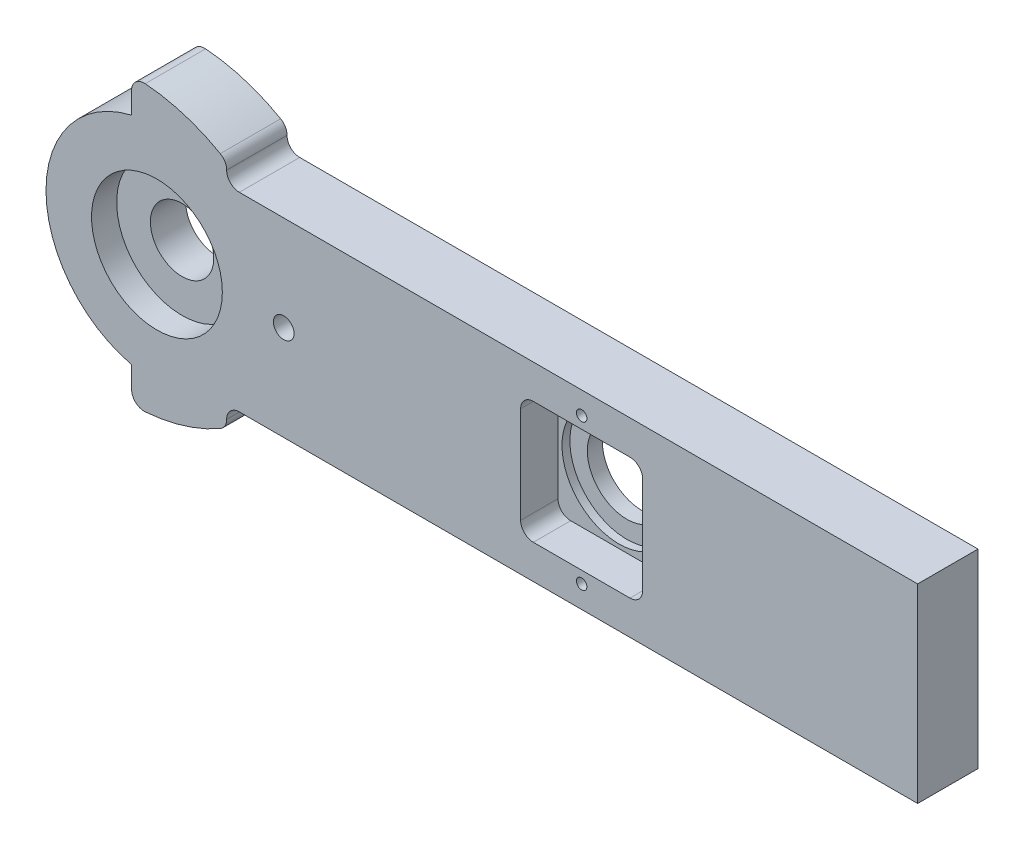
SolidWorks part; units mm, degrees
material "PE High Density"
ref_plane "Front Plane" through (0, 0, 0) normal (0, 0, 1) x (1, 0, 0)
ref_plane "Top Plane" through (0, 0, 0) normal (0, 1, 0) x (1, 0, 0)
ref_plane "Right Plane" through (0, 0, 0) normal (1, 0, 0) x (0, 0, -1)
sketch "Sketch1" plane through (0, 0, 0) normal (0, 0, 1) x (1, 0, 0)
  line L0 (30, 0) -> (30, 30) construction
  line L3 (0, 30) -> (18.0278, 30) construction
  line L6 (0, 0) -> (30, 0) construction
  line L8 (18.0278, 30) -> (240, 30)
  line L9 (240, 30) -> (240, -30)
  line L11 (18.0278, -30) -> (240, -30)
  circle A0 centre (0, 0) radius 30 construction
  arc A2 (18.0278, 30) -> (18.0278, -30) centre (0, 0) ccw
  circle A5 centre (0, 0) radius 10
  dimension "D1" = 60
  dimension "D4" = 70
  dimension "D8" = 20
  dimension "D2" = 240
extrude "Boss-Extrude1" add sketch "Sketch1" along normal mid plane 19.05
sketch "Sketch2" plane through (0, 0, -9.525) normal (0, 0, 1) x (1, 0, 0)
  line L0 (240, -30) -> (240, 30) construction
  circle A0 centre (134, 0) radius 12.5
  dimension "D2" = 25
  dimension "D1" = 106
extrude "Cut-Extrude1" cut sketch "Sketch2" along normal through all
sketch "Sketch3" plane through (0, 0, 9.525) normal (0, 0, 1) x (1, 0, 0)
  line L1 (114.5, -19.5) -> (153.5, -19.5) construction
  line L2 (114.5, -19.5) -> (114.5, 19.5) construction
  line L3 (114.5, 19.5) -> (153.5, 19.5) construction
  line L4 (153.5, -19.5) -> (153.5, 19.5) construction
  line L5 (114.5, -19.5) -> (153.5, 19.5) construction
  line L6 (114.5, 19.5) -> (153.5, -19.5) construction
  circle A0 centre (134, 0) radius 12.5 construction
  circle A3 centre (134, 0) radius 18
  dimension "D1" = 36
  dimension "D2" = 39
  dimension "D3" = 39
extrude "Cut-Extrude2" cut sketch "Sketch3" against normal blind 14.2875
sketch "Sketch4" plane through (0, 0, 9.525) normal (0, 0, 1) x (1, 0, 0)
  circle A0 centre (0, 0) radius 20.6375
  dimension "D1" = 41.275
extrude "Cut-Extrude3" cut sketch "Sketch4" against normal blind 7.9375
sketch "Sketch5" plane through (0, 0, 9.525) normal (0, 0, 1) x (1, 0, 0)
  line L1 (114.75, -19.25) -> (153.25, -19.25)
  line L2 (114.75, -19.25) -> (114.75, 19.25)
  line L3 (114.75, 19.25) -> (153.25, 19.25)
  line L4 (153.25, -19.25) -> (153.25, 19.25)
  line L5 (114.75, -19.25) -> (153.25, 19.25) construction
  line L6 (114.75, 19.25) -> (153.25, -19.25) construction
  point P0 (134, 0)
  dimension "D1" = 38.5
  dimension "D2" = 38.5
extrude "Cut-Extrude4" cut sketch "Sketch5" against normal offset from surface (11.7875 mm away) 2.5 up to face at (146.5, 0, -4.7625)
fillet "Fillet3" radius 4 4 edges at (153.25, -19.25, 3.6313) (114.75, -19.25, 3.6313) (153.25, 19.25, 3.6313) (114.75, 19.25, 3.6313)
sketch "Sketch12" plane through (0, 0, 9.525) normal (0, 0, 1) x (1, 0, 0)
  line L1 (240, 30) -> (18.0278, 30) construction
  line L3 (22, 30) -> (22, 36.35)
  line L4 (-8, 45) -> (22, 45) construction
  line L5 (-8, 45) -> (-8, 34.0735)
  line L6 (240, 30) -> (18.0278, 30) construction
  line L7 (22, 30) -> (18.0278, 30)
  arc A0 (-8, 45) -> (22, 36.35) centre (-8, -11.3481) cw
  arc A1 (18.0278, 30) -> (18.0278, -30) centre (0, 0) ccw construction
  arc A2 (18.0278, 30) -> (-8, 34.0735) centre (0, 0) ccw
  dimension "D2" = 6.35
  dimension "D3" = 30
  dimension "D1" = 45
  dimension "D4" = 8
extrude "Boss-Extrude2" add sketch "Sketch12" against normal through all
mirror "Mirror4" about plane through (0, 0, 0) normal (0, 1, 0) of "Boss-Extrude2"
fillet "Fillet4" radius 4 4 edges at (22, 36.35, 0) (22, -36.35, 0) (-8, -45, 0) (-8, 45, 0)
fillet "Fillet6" radius 4 2 edges at (22, 30, 0) (22, -30, 0)
sketch "Sketch14" plane through (0, 0, 9.525) normal (0, 0, 1) x (1, 0, 0)
  line L0 (0, 0) -> (40, 0) construction
  line L1 (0, 0) -> (40, 0) construction
  circle A0 centre (0, 0) radius 40 construction
  circle A1 centre (40, 0) radius 3.2639
  dimension "D1" = 80
  dimension "D2" = 6.5278
  dimension "D3" = 0
extrude "Cut-Extrude6" cut sketch "Sketch14" against normal through all
sketch "Sketch15" plane through (0, 0, 9.525) normal (0, 0, 1) x (1, 0, 0)
  line L0 (134, 0) -> (134, 23) construction
  line L1 (240, 30) -> (26, 30) construction
  line L2 (134, 0) -> (146.5, 0) construction
  circle A0 centre (134, 0) radius 12.5 construction
  point P0 (134, 23)
  point P9 (134, -23)
  dimension "D1" = 7
hole_wizard "M4x0.7 Tapped Hole1" positions "Sketch16" profile "Sketch17" tap size "M4x0.7" standard "ANSI Metric" end condition through all
sketch "Sketch16" plane through (0, 0, -9.525) normal (0, 0, -1) x (-1, 0, 0)
  point P0 (-134, 23)
  point P3 (-134, -23)
sketch "Sketch17" plane through (134, 23, -9.525) normal (1, 0, 0) x (0, 1, 0)
  line L0 (0, 0) -> (0, 19.05)
  line L1 (0, 19.05) -> (1.65, 19.05)
  line L2 (1.65, 19.05) -> (1.65, 0)
  line L5 (1.65, 0) -> (0, 0)
  line L11 (0, -6.35) -> (0, 107.95) construction
  dimension "Thru Tap Drill Dia." = 3.3
  dimension "Thru Tap Drill Depth" = 19.05
cosmetic thread "Hole Thread1" parameters "D2"=4
cosmetic thread "Hole Thread2" parameters "D2"=4
equation "\"D1@Boss-Extrude1\"=0.75in"
equation "\"D1@Sketch4\"=1.625in"
equation "\"D1@Sketch1\"=60"
equation "\"D1@Cut-Extrude2\"=8.000000mm+6.2875"
equation "\"D2@Sketch12\"=0.25in"
equation "\"D2@Sketch14\"=0.257in"
